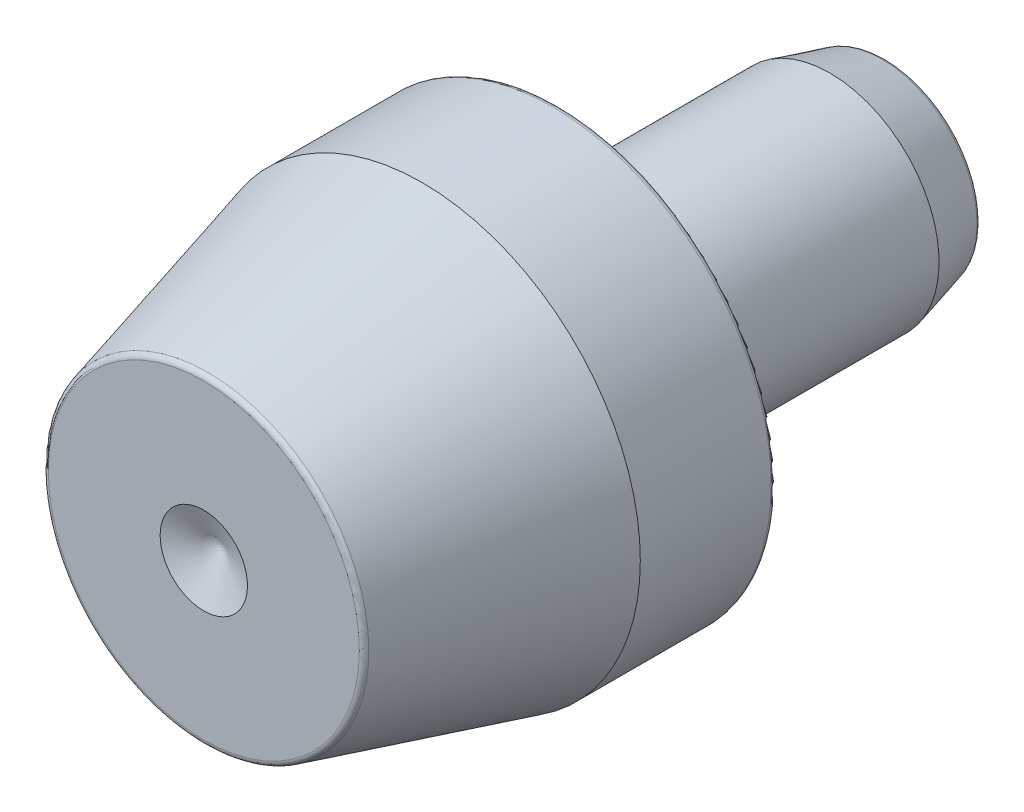
SolidWorks part; units mm, degrees
ref_plane "Front Plane" through (0, 0, 0) normal (0, 0, 1) x (1, 0, 0)
ref_plane "Top Plane" through (0, 0, 0) normal (0, 1, 0) x (1, 0, 0)
ref_plane "Right Plane" through (0, 0, 0) normal (1, 0, 0) x (0, 0, -1)
sketch "Sketch1" plane through (0, 0, 0) normal (1, 0, 0) x (0, 0, -1)
  line L0 (-12.5, 0) -> (12.5, 0) construction
  line L1 (-12.5, 1.6) -> (-12.5, 5.6991)
  line L2 (-12.3481, 5.8971) -> (-4.5, 8)
  line L3 (-4.5, 8) -> (0.295, 8)
  line L4 (0.5, 7.795) -> (0.5, 4.615)
  line L5 (1.73, 4) -> (10.45, 4)
  line L6 (10.45, 4) -> (12.3481, 3.4914)
  line L7 (12.5, 3.2934) -> (12.5, 0)
  line L8 (12.5, 0) -> (-11.8373, 0)
  line L9 (-12.5, 1.6) -> (-11.8373, 0)
  line L10 (-12.5, 1.6) -> (-12.5, 0) construction
  line L12 (0.295, 4.41) -> (0.295, 4)
  line L13 (0.5, 3.795) -> (1.525, 3.795)
  line L14 (1.525, 3.795) -> (1.73, 4)
  arc A0 (0.5, 4.615) -> (0.295, 4.41) centre (0.5, 4.41) ccw
  arc A1 (0.295, 4) -> (0.5, 3.795) centre (0.5, 4) ccw
  arc A2 (0.5, 7.795) -> (0.295, 8) centre (0.295, 7.795) ccw
  arc A3 (-12.5, 5.6991) -> (-12.3481, 5.8971) centre (-12.295, 5.6991) cw
  arc A4 (12.5, 3.2934) -> (12.3481, 3.4914) centre (12.295, 3.2934) ccw
  point P20 (-12.5, 5.8564)
  point P25 (12.5, 3.4507)
  dimension "D5" = 15
  dimension "D6" = 15
  dimension "D1" = 22.5
  dimension "D2" = 1.6
  dimension "D3" = 45
  dimension "D7" = 0.205
  dimension "D8" = 0.205
  dimension "D9" = 0.615
  dimension "D10" = 1.025
revolve "Revolve1" add sketch "Sketch1" angle 360 about L8
ref_plane "Contact Plane 1" through (0, 0, 12.5) normal (0, 0, 1) x (1, 0, 0)
ref_axis "Center Axis 1" through (0, 0, -7.15) along (0, 0, 1)
equation "\"D4@Sketch1\"=\"C@Sketch1\"*.25625"
equation "\"D2@Sketch1\"=\"A@Sketch1\"*.1"
equation "\"D7@Sketch1\"=\"D4@Sketch1\"*.1"
equation "\"D8@Sketch1\"=\"D7@Sketch1\""
equation "\"D9@Sketch1\"=\"D7@Sketch1\"*3"
equation "\"D10@Sketch1\"=\"D4@Sketch1\"*.5"
